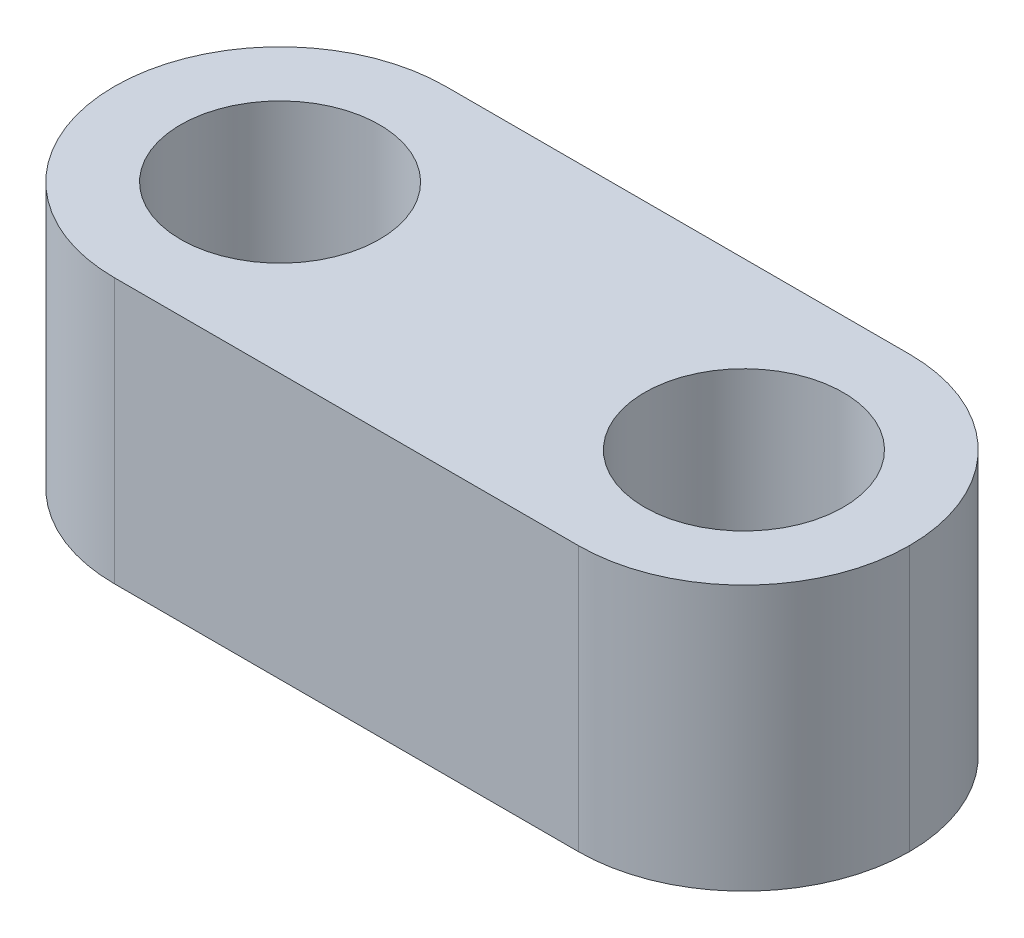
SolidWorks part; units mm, degrees
ref_plane "Front Plane" through (0, 0, 0) normal (0, 0, 1) x (1, 0, 0)
ref_plane "Top Plane" through (0, 0, 0) normal (0, 1, 0) x (1, 0, 0)
ref_plane "Right Plane" through (0, 0, 0) normal (1, 0, 0) x (0, 0, -1)
sketch "Sketch1" plane through (0, 0, 0) normal (0, 1, 0) x (1, 0, 0)
  line L1 (-6, 2.5) -> (6, 2.5)
  line L2 (-6, 2.5) -> (-6, -2.5)
  line L3 (-6, -2.5) -> (6, -2.5)
  line L4 (6, 2.5) -> (6, -2.5)
  line L5 (-6, 2.5) -> (6, -2.5) construction
  line L6 (-6, -2.5) -> (6, 2.5) construction
  point P0 (0, 0)
  dimension "D1" = 12
  dimension "D2" = 5
extrude "Boss-Extrude1" add sketch "Sketch1" along normal blind 4
sketch "Sketch2" plane through (0, 4, 0) normal (0, 1, 0) x (1, 0, 0)
  line L1 (6, -2.5) -> (6, 2.5) construction
  circle A0 centre (3.5, 0) radius 1.5
  dimension "D1" = 3
  dimension "D2" = 2.5
extrude "Cut-Extrude1" cut sketch "Sketch2" against normal blind 4
sketch "Sketch3" plane through (0, 4, 0) normal (0, 1, 0) x (1, 0, 0)
  line L0 (-6, 2.5) -> (-6, -2.5) construction
  circle A0 centre (-3.5, 0) radius 1.5
  dimension "D1" = 3
  dimension "D2" = 2.5
extrude "Cut-Extrude2" cut sketch "Sketch3" against normal blind 4
fillet "Fillet1" radius 2.5 4 edges at (6, 2, 2.5) (6, 2, -2.5) (-6, 2, 2.5) (-6, 2, -2.5)
